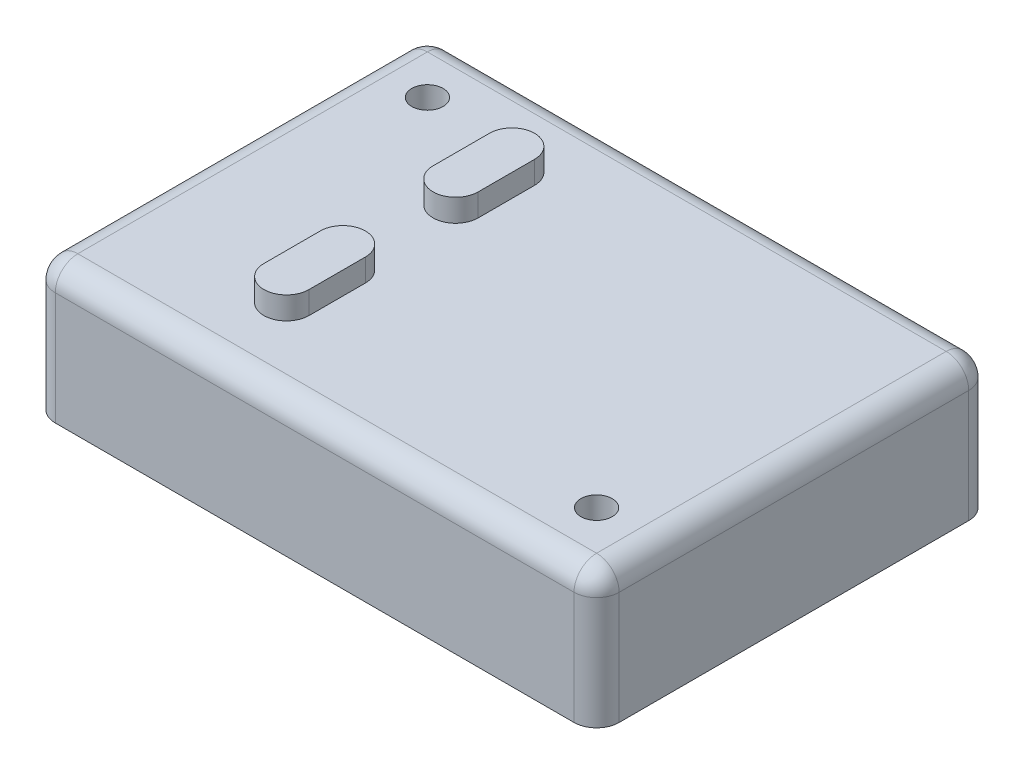
SolidWorks part; units mm, degrees
ref_plane "Front Plane" through (0, 0, 0) normal (0, 0, 1) x (1, 0, 0)
ref_plane "Top Plane" through (0, 0, 0) normal (0, 1, 0) x (1, 0, 0)
ref_plane "Right Plane" through (0, 0, 0) normal (1, 0, 0) x (0, 0, -1)
sketch "Sketch1" plane through (0, 0, 0) normal (0, 1, 0) x (1, 0, 0)
  line L1 (-25, -17.5) -> (25, -17.5)
  line L2 (-25, -17.5) -> (-25, 17.5)
  line L3 (-25, 17.5) -> (25, 17.5)
  line L4 (25, -17.5) -> (25, 17.5)
  line L5 (-25, -17.5) -> (25, 17.5) construction
  line L6 (-25, 17.5) -> (25, -17.5) construction
  point P0 (0, 0)
  dimension "D1" = 50
  dimension "D2" = 35
extrude "Boss-Extrude1" add sketch "Sketch1" along normal blind 12
sketch "Sketch2" plane through (0, 12, 0) normal (0, 1, 0) x (1, 0, 0)
  line L0 (-10, 10) -> (-10, 5) construction
  line L1 (-8, 10) -> (-8, 5)
  line L2 (-12, 10) -> (-12, 5)
  line L3 (-10, -5) -> (-10, -10) construction
  line L4 (-8, -5) -> (-8, -10)
  line L5 (-12, -5) -> (-12, -10)
  arc A0 (-8, 10) -> (-12, 10) centre (-10, 10) ccw
  arc A1 (-12, 5) -> (-8, 5) centre (-10, 5) ccw
  arc A2 (-8, -5) -> (-12, -5) centre (-10, -5) ccw
  arc A3 (-12, -10) -> (-8, -10) centre (-10, -10) ccw
  point P2 (-10, 7.5)
  point P7 (-10, -7.5)
  dimension "D3" = 2
  dimension "D1" = 15
  dimension "D2" = 7.5
  dimension "D4" = 5
  dimension "D5" = 10
extrude "Boss-Extrude2" add sketch "Sketch2" along normal blind 2
fillet "Fillet1" radius 2 8 edges at (-25, 12, 0) (0, 12, -17.5) (-25, 6, -17.5) (25, 12, 0) (25, 6, -17.5) (-25, 6, 17.5) (0, 12, 17.5) (25, 6, 17.5)
sketch "Sketch4" plane through (0, 0, 0) normal (0, -1, 0) x (1, 0, 0)
  line L0 (23, -17.5) -> (-23, -17.5) construction
  line L1 (25, 15.5) -> (25, -15.5) construction
  line L2 (-25, -15.5) -> (-25, 15.5) construction
  line L4 (-23, 17.5) -> (23, 17.5) construction
  circle A0 centre (-19.5, -12) radius 1.39
  circle A1 centre (19.5, 12) radius 1.39
  dimension "D1" = 2.78
  dimension "D2" = 5.5
  dimension "D3" = 5.5
  dimension "D4" = 5.5
  dimension "D5" = 5.5
extrude "Cut-Extrude1" cut sketch "Sketch4" against normal through all
equation "\"D2@Sketch2\"=\"D1@Sketch2\"/2"
